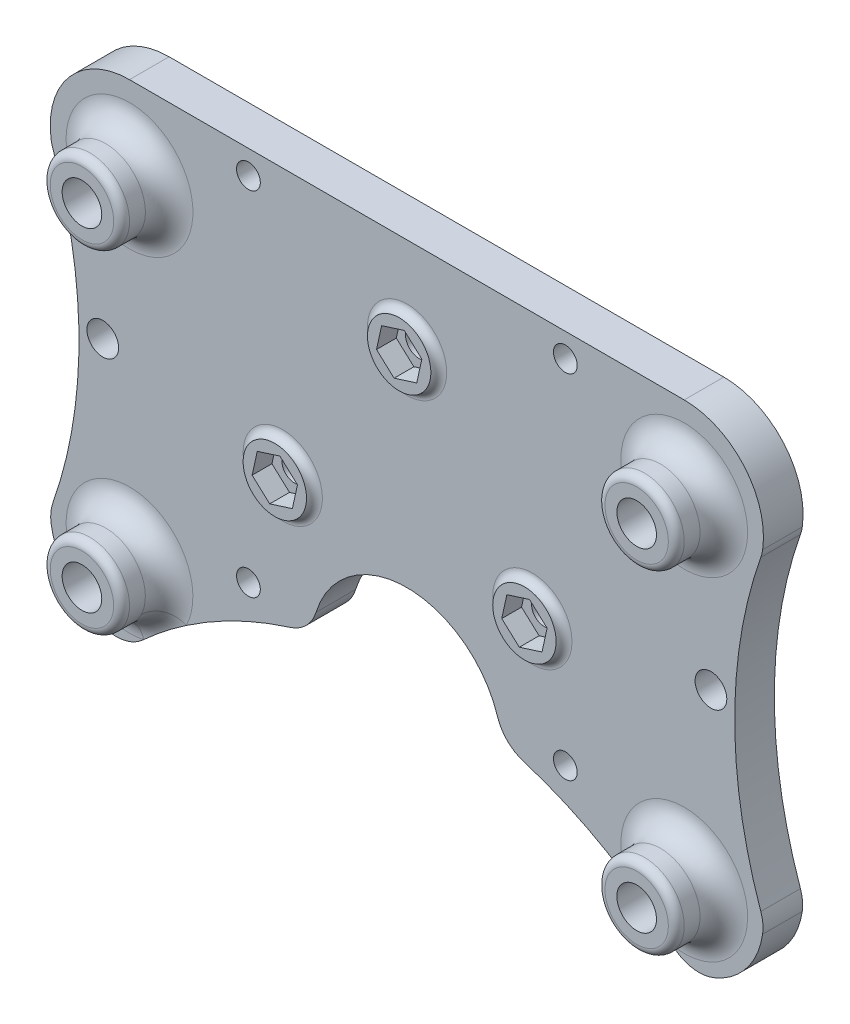
SolidWorks part; units mm, degrees
ref_plane "Front Plane" through (0, 0, 0) normal (0, 0, 1) x (1, 0, 0)
ref_plane "Top Plane" through (0, 0, 0) normal (0, 1, 0) x (1, 0, 0)
ref_plane "Right Plane" through (0, 0, 0) normal (1, 0, 0) x (0, 0, -1)
sketch "Sketch1" plane through (0, 0, 0) normal (0, 0, 1) x (1, 0, 0)
  line L0 (-35, -9.5) -> (35, -9.5) construction
  line L1 (-35, 32.5) -> (35, 32.5) construction
  line L2 (0, 43) -> (0, -55.1813) construction
  line L3 (-35, 43) -> (35, 43)
  line L4 (-35, 32.5) -> (-35, -9.5) construction
  line L5 (35, 33) -> (35, -9.5) construction
  circle A0 centre (-35, 32.5) radius 2.5
  circle A1 centre (35, 32.5) radius 2.5
  circle A2 centre (-35, -9.5) radius 2.5
  circle A3 centre (35, -9.5) radius 2.5
  arc A4 (35, 43) -> (44.7979, 30.9995) centre (35, 33) cw
  arc A5 (45, -9) -> (35.245, -19) centre (35, -9.003) cw
  arc A6 (-35, -19) -> (-45, -9) centre (-35, -9) cw
  arc A7 (-44.7979, 30.9995) -> (-35, 43) centre (-35, 33) cw
  arc A8 (-44.7979, 30.9995) -> (-45, -9) centre (-99.8573, 11.2775) cw
  arc A9 (44.7979, 30.9995) -> (45, -9) centre (99.8573, 11.2775) ccw
  arc A10 (-35, -19) -> (35.245, -19) centre (0.1225, -54.1225) cw
  point P0 (0, 0)
  point P6 (0, 0)
  point P18 (45, 40)
  dimension "D5" = 10
  dimension "D2" = 40
  dimension "D1" = 10.5
  dimension "D3" = 42
  dimension "D4" = 70
extrude "Boss-Extrude1" add sketch "Sketch1" along normal blind 5
sketch "Sketch2" plane through (0, 0, 5) normal (0, 0, 1) x (1, 0, 0)
  circle A0 centre (-35, 32.5) radius 5.0046
  circle A1 centre (35, 32.5) radius 5
  circle A2 centre (-35, -9.5) radius 5
  circle A3 centre (35, -9.5) radius 5
  circle A4 centre (-35, 32.5) radius 2.5
  circle A5 centre (35, 32.5) radius 2.5
  circle A6 centre (35, -9.5) radius 2.5
  circle A7 centre (-35, -9.5) radius 2.5
extrude "Boss-Extrude2" add sketch "Sketch2" along normal blind 6
chamfer "Chamfer1" distance 3 angle 45 4 edges at (37.5, -9.5, 0) (-32.5, -9.5, 0) (-32.5, 32.5, 0) (37.5, 32.5, 0)
fillet "Fillet1" radius 3 4 edges at (-40, -9.5, 5) (30, -9.5, 5) (30, 32.5, 5) (-40.0046, 32.5, 5)
fillet "Fillet2" radius 1 4 edges at (-30, -9.5, 11) (40, -9.5, 11) (40, 32.5, 11) (-29.9954, 32.5, 11)
sketch "Sketch3" plane through (0, 0, 0) normal (0, 0, -1) x (-1, 0, 0)
  line L0 (-35, 43) -> (35, 43) construction
  line L1 (0, 43) -> (-0.1225, -4.4518) construction
  circle A0 centre (0, -7) radius 12
  arc A1 (35, -19) -> (-35.245, -19) centre (-0.1225, -54.1225) ccw construction
  circle A2 centre (-15.8365, 9.5) radius 1.6
  circle A3 centre (15.6634, 9.4187) radius 1.6
  circle A4 centre (-0.031, 31) radius 1.7
  circle A5 centre (-38.373, 13) radius 2
  circle A6 centre (38.373, 13) radius 2
  circle A7 centre (19.9923, 40) radius 1.5
  circle A8 centre (-20, 40) radius 1.5
  arc A9 (-45, -9) -> (-44.7979, 30.9995) centre (-99.8573, 11.2775) ccw construction
  arc A10 (44.7979, 30.9995) -> (45, -9) centre (99.8573, 11.2775) ccw construction
  circle A11 centre (-20, -4.4518) radius 1.5
  circle A12 centre (19.9923, -4.4518) radius 1.5
  point P22 (-41.373, 10.9819)
  point P26 (41.373, 10.9819)
  dimension "D1" = 50
  dimension "D2" = 15.75
  dimension "D4" = 12
  dimension "D5" = 3
  dimension "D9" = 3
  dimension "D3" = 33.5
  dimension "D6" = 3
  dimension "D7" = 30
  dimension "D8" = 30
  dimension "D10" = 20
  dimension "D11" = 20
  dimension "D12" = 3
extrude "Cut-Extrude1" cut sketch "Sketch3" against normal up to next
fillet "Fillet3" radius 5 8 edges at (-44.7979, 30.9995, 2.5) (-45, -9, 2.5) (-35, -19, 2.5) (-11.9533, -5.9421, 2.5) (11.9476, -5.8799, 2.5) (35.245, -19, 2.5) (45, -9, 2.5) (44.7979, 30.9995, 2.5)
sketch "Sketch4" plane through (0, 0, 5) normal (0, 0, 1) x (1, 0, 0)
  line L1 (0.7316, 29.9953) -> (1.2514, 31.1044)
  line L2 (1.2514, 31.1044) -> (0.5508, 32.1091)
  line L3 (0.5508, 32.1091) -> (-0.6696, 32.0047)
  line L4 (-0.6696, 32.0047) -> (-1.1894, 30.8956)
  line L5 (-1.1894, 30.8956) -> (-0.4888, 29.8909)
  line L6 (-0.4888, 29.8909) -> (0.7316, 29.9953)
  line L7 (-14.9624, 8.413) -> (-14.442, 9.5229)
  line L8 (-14.442, 9.5229) -> (-15.143, 10.5286)
  line L9 (-15.143, 10.5286) -> (-16.3644, 10.4243)
  line L10 (-16.3644, 10.4243) -> (-16.8848, 9.3144)
  line L11 (-16.8848, 9.3144) -> (-16.1838, 8.3088)
  line L12 (-16.1838, 8.3088) -> (-14.9624, 8.413)
  line L13 (16.54, 8.4933) -> (17.06, 9.6059)
  line L14 (17.06, 9.6059) -> (16.3566, 10.6125)
  line L15 (16.3566, 10.6125) -> (15.1331, 10.5067)
  line L16 (15.1331, 10.5067) -> (14.613, 9.3941)
  line L17 (14.613, 9.3941) -> (15.3165, 8.3875)
  line L18 (15.3165, 8.3875) -> (16.54, 8.4933)
  circle A0 centre (0.031, 31) radius 4
  circle A1 centre (0.031, 31) radius 1.0608 construction
  circle A2 centre (-15.6634, 9.4187) radius 4
  circle A3 centre (15.8365, 9.5) radius 4
  circle A4 centre (-15.6634, 9.4187) radius 1.0616 construction
  circle A5 centre (15.8365, 9.5) radius 1.0636 construction
extrude "Boss-Extrude3" add sketch "Sketch4" along normal blind 1
fillet "Fillet4" radius 1 3 edges at (-3.969, 31, 5) (11.8365, 9.5, 5) (-19.6634, 9.4187, 5)
sketch "Sketch5" plane through (0, 0, 5) normal (0, 0, 1) x (1, 0, 0)
  line L1 (2.2481, 28.9757) -> (2.8926, 31.9079)
  line L2 (2.8926, 31.9079) -> (0.6755, 33.9322)
  line L3 (0.6755, 33.9322) -> (-2.1861, 33.0243)
  line L4 (-2.1861, 33.0243) -> (-2.8307, 30.0921)
  line L5 (-2.8307, 30.0921) -> (-0.6136, 28.0678)
  line L6 (-0.6136, 28.0678) -> (2.2481, 28.9757)
  line L7 (18.0541, 7.4762) -> (18.698, 10.4085)
  line L8 (18.698, 10.4085) -> (16.4804, 12.4324)
  line L9 (16.4804, 12.4324) -> (13.619, 11.5238)
  line L10 (13.619, 11.5238) -> (12.9751, 8.5915)
  line L11 (12.9751, 8.5915) -> (15.1926, 6.5676)
  line L12 (15.1926, 6.5676) -> (18.0541, 7.4762)
  line L13 (-13.4471, 7.3935) -> (-12.8014, 10.3254)
  line L14 (-12.8014, 10.3254) -> (-15.0176, 12.3506)
  line L15 (-15.0176, 12.3506) -> (-17.8797, 11.4439)
  line L16 (-17.8797, 11.4439) -> (-18.5254, 8.5119)
  line L17 (-18.5254, 8.5119) -> (-16.3091, 6.4867)
  line L18 (-16.3091, 6.4867) -> (-13.4471, 7.3935)
  circle A0 centre (0.031, 31) radius 2.6 construction
  circle A1 centre (15.8365, 9.5) radius 2.6 construction
  circle A2 centre (-15.6634, 9.4187) radius 2.6 construction
extrude "Cut-Extrude2" cut sketch "Sketch5" against normal blind 1.5 and the other way up to next
